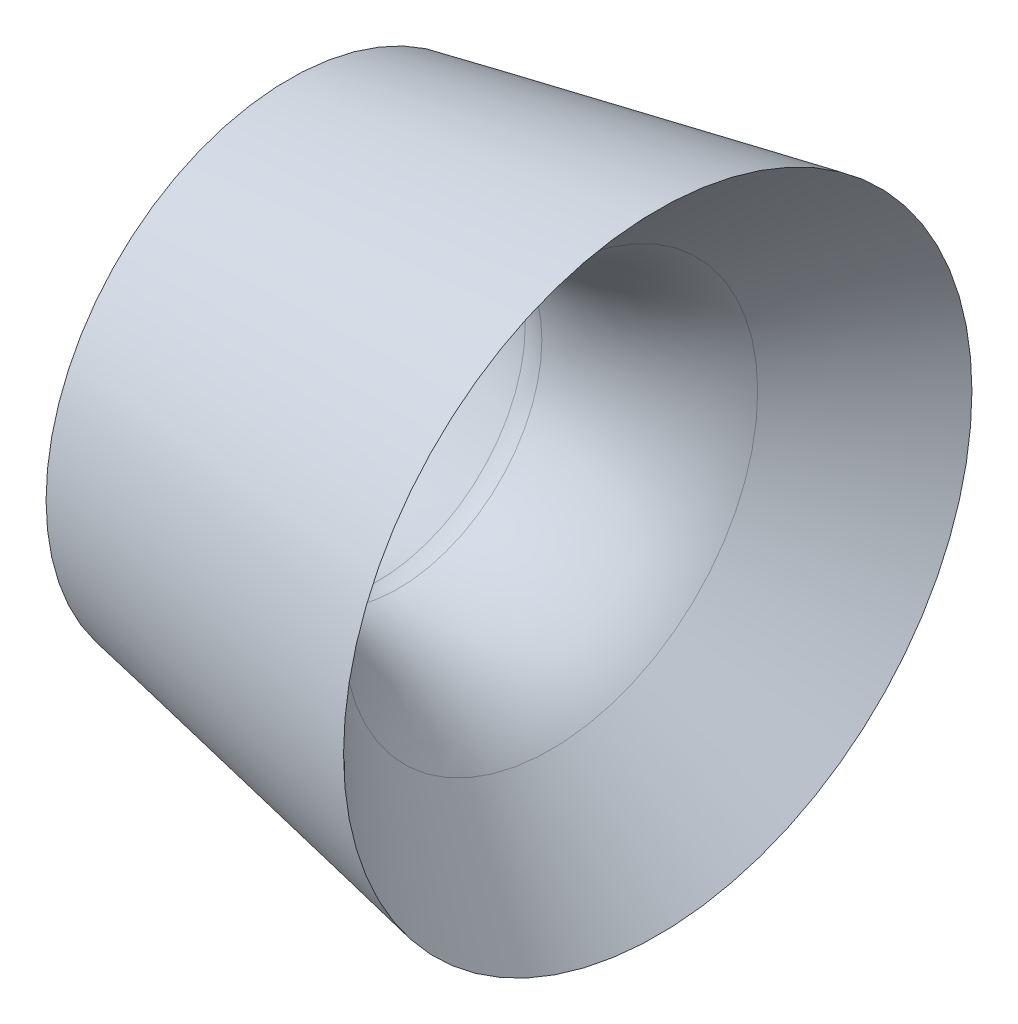
SolidWorks part; units mm, degrees
material "C (Graphite)"
ref_plane "Front Plane" through (0, 0, 0) normal (0, 0, 1) x (1, 0, 0)
ref_plane "Top Plane" through (0, 0, 0) normal (0, 1, 0) x (1, 0, 0)
ref_plane "Right Plane" through (0, 0, 0) normal (1, 0, 0) x (0, 0, -1)
sketch "Sketch1" plane through (0, 0, 0) normal (0, 0, 1) x (1, 0, 0)
  line L1 (0, 24.472) -> (-8.3426, 16.1295)
  line L3 (0, 0) -> (-30, 0) construction
  line L5 (-30, 18.6909) -> (-30, 14.6909) construction
  line L6 (-30, 18.6909) -> (-28.7014, 18.9412) construction
  line L8 (0, 24.472) -> (-30, 24.472) construction
  line L10 (0, 24.472) -> (0, 0) construction
  line L11 (-28.7014, 18.9412) -> (-28.7014, 14.2061)
  line L12 (-28.7014, 18.9412) -> (0, 24.472)
  arc A1 (-8.3426, 16.1295) -> (-20.2285, 11.2061) centre (-20.2285, 28.0154) cw
  arc A2 (-20.2285, 11.2061) -> (-21.8411, 11.5215) centre (-20.2285, 15.4869) cw
  arc A4 (-21.8411, 11.5215) -> (-28.7014, 14.2061) centre (-126.69, -246.3001) ccw
  arc A5 (-28.7014, 14.2061) -> (-30, 14.6909) centre (-126.69, -246.3001) ccw construction
  dimension "D11" = 4.2807
  dimension "D12" = 16.8092
  dimension "D4" = 278.3258
  dimension "D6" = 4
  dimension "D20" = 30
  dimension "D3" = 10.907
  dimension "D5" = 24.472
  dimension "D7" = 11.2061
  dimension "D8" = 3
  dimension "D9" = 45
  dimension "D15" = 22.13
revolve "Revolve1" add sketch "Sketch1" angle 360 about L3 region at (-16.1948, 17.4006, 0)
equation "\"theta_t\"= 36.9009 - ( 426.271 / ( \"Aet\" + 7.00037 ) ) + ( 10026.8 / ( \"Aet\" + 7.00037 ) ^ 2 ) - ( 175410 / ( \"Aet\" + 7.00037 ) ^ 3 ) + ( ( 1.6742 * ( 10 ^ 6 ) ) / ( \"Aet\" + 7.00037 ) ^ 4 ) - ( ( 6.7643 * ( 10 ^ 6 ) ) / ( \"Aet\" + 7.00037 ) ^ 5 )"
equation "\"rt\"= ( 0.022412299 / 2 ) * 1000"
equation "\"re\"= sqr ( \"rt\" ^ 2 * \"Aet\" )"
equation "\"Aet\"= 4.317"
equation "\"L\"= 0.8 * ( ( \"re\" / tan ( 15 ) ) - ( \"rt\" / tan ( 15 ) ) )"
equation "\"lc\"= ( \"l*\" / \"cr\" )"
equation "\"b\"= tan ( \"theta_t\" )"
equation "\"a\"= ( \"re\" - \"b\" * \"L\" - \"c\" ) / \"L\" ^ 2"
equation "\"D11@Sketch1\"=0.382*\"rt\""
equation "\"D12@Sketch1\"=1.5*\"rt\""
equation "\"c\"= \"rt\" * ( 1.382 - 0.382 * cos ( \"theta_t\" ) )"
equation "\"D15@Sketch1\"=\"theta_t\""
equation "\"cr\"= 5.978857531"
equation "\"rc\"= sqr ( \"cr\" * ( \"rt\" ^ 2 ) )"
equation "\"l*\"= 1000"
equation "\"th\"= 10"
equation "\"theta_cr\"= 45deg"
equation "\"D9@Sketch1\"=\"theta_cr\""
